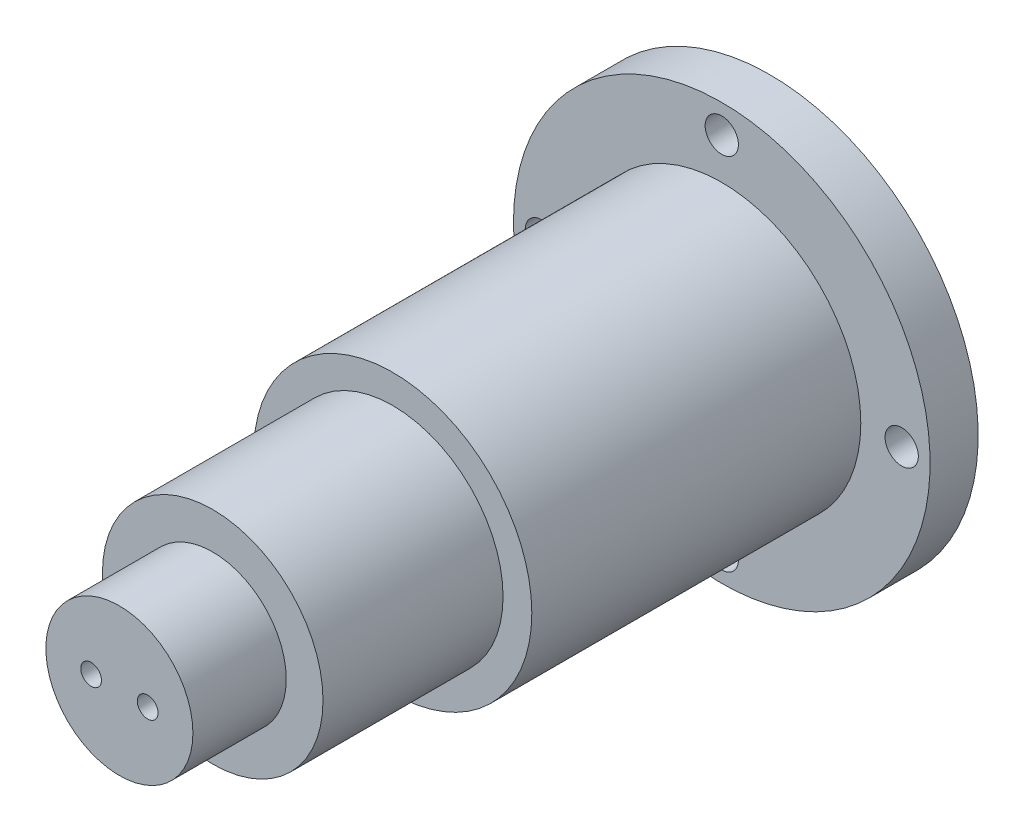
SolidWorks part; units mm, degrees
ref_plane "Front Plane" through (0, 0, 0) normal (0, 0, 1) x (1, 0, 0)
ref_plane "Top Plane" through (0, 0, 0) normal (0, 1, 0) x (1, 0, 0)
ref_plane "Right Plane" through (0, 0, 0) normal (1, 0, 0) x (0, 0, -1)
ref_plane "Plane1" through (0, 0, 0) normal (0, -1, 0) x (1, 0, 0)
sketch "Sketch1" plane through (0, 0, 0) normal (0, -1, 0) x (1, 0, 0)
  line L0 (22.1, 5.1) -> (0, 5.1)
  line L1 (0, 5.1) -> (0, 0)
  line L2 (0, 0) -> (22.1, 0)
  line L3 (22.1, 0) -> (22.1, 5.1)
  line L4 (0, 5.1) -> (0, 0) construction
revolve "Revolve1" add sketch "Sketch1" angle 360 about L4 reverse direction yes
sketch "Sketch2" plane through (0, 0, 5.1) normal (0, 0, 1) x (1, 0, 0)
  circle A0 centre (0, 0) radius 14.75
extrude "Boss-Extrude1" add sketch "Sketch2" along normal blind 34.9
sketch "Sketch3" plane through (0, 0, 40) normal (0, 0, 1) x (1, 0, 0)
  circle A0 centre (0, 0) radius 11.7
extrude "Boss-Extrude2" add sketch "Sketch3" along normal blind 19.1
sketch "Sketch4" plane through (0, 0, 59.1) normal (0, 0, 1) x (1, 0, 0)
  circle A0 centre (0, 0) radius 7.8
extrude "Boss-Extrude3" add sketch "Sketch4" along normal blind 9.9
hole_wizard "M10 Clearance Hole1" positions "Sketch6" profile "Sketch5" hole size "M10" standard "ANSI Metric"
sketch "Sketch6" plane through (0, 0, 0) normal (0, 0, -1) x (-1, 0, 0)
  point P0 (0, 0)
sketch "Sketch5" plane through (0, 0, 0) normal (1, 0, 0) x (0, 1, 0)
  line L0 (0, 0) -> (0, 22.6255)
  line L1 (0, 22.6255) -> (6.35, 18.81)
  line L2 (6.35, 18.81) -> (6.35, 0)
  line L5 (6.35, 0) -> (0, 0)
  line L10 (0, 22.6255) -> (-6.35, 18.81) construction
  line L11 (0, -6.35) -> (0, 107.95) construction
  dimension "Hole Dia." = 12.7
  dimension "Hole Depth" = 18.81
  dimension "Drill Angle" = 118
hole_wizard "Ø2.2 (2.2) Diameter Hole1" positions "Sketch8" profile "Sketch7" hole size "Ø2.2" standard "ANSI Metric"
sketch "Sketch8" plane through (0, 0, 69) normal (0, 0, 1) x (1, 0, 0)
  point P0 (-3, 0)
  point P1 (3, 0)
sketch "Sketch7" plane through (-3, 0, 69) normal (1, 0, 0) x (0, -1, 0)
  line L0 (0, 0) -> (0, 15)
  line L1 (0, 15) -> (1.1, 15)
  line L2 (1.1, 15) -> (1.1, 0)
  line L5 (1.1, 0) -> (0, 0)
  line L10 (0, 15) -> (-1.1, 15) construction
  line L11 (0, -6.35) -> (0, 107.95) construction
  dimension "Hole Dia." = 2.2
  dimension "Hole Depth" = 15
  dimension "Drill Angle" = 180
hole_wizard "M3 Clearance Hole1" positions "Sketch10" profile "Sketch9" hole size "M3" standard "ANSI Metric"
sketch "Sketch10" plane through (0, 0, 0) normal (0, 0, -1) x (-1, 0, 0)
  point P0 (0, 19.0875)
  point P1 (-19.0875, 0)
  point P2 (0, -19.0875)
  point P3 (19.0875, 0)
sketch "Sketch9" plane through (0, 19.0875, 0) normal (1, 0, 0) x (0, 1, 0)
  line L0 (0, 0) -> (0, 69)
  line L1 (0, 69) -> (1.765, 69)
  line L2 (1.765, 69) -> (1.765, 0)
  line L5 (1.765, 0) -> (0, 0)
  line L11 (0, -6.35) -> (0, 107.95) construction
  dimension "Thru Hole Dia." = 3.53
  dimension "Thru Hole Depth" = 69
chamfer "Chamfer1" distance 2 angle 45 1 edges at (-6.35, 0, 0)
